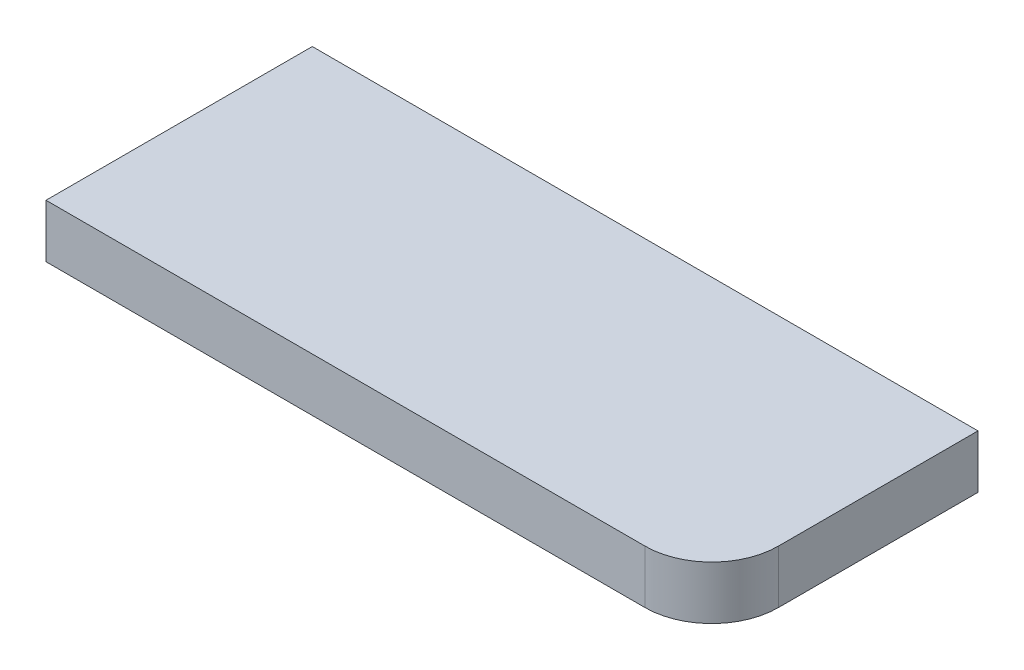
SolidWorks part; units mm, degrees
material "Клен"
ref_plane "Спереди" through (0, 0, 0) normal (0, 0, 1) x (1, 0, 0)
ref_plane "Сверху" through (0, 0, 0) normal (0, 1, 0) x (1, 0, 0)
ref_plane "Справа" through (0, 0, 0) normal (1, 0, 0) x (0, 0, -1)
sketch "Эскиз1" plane through (0, 0, 0) normal (0, 1, 0) x (1, 0, 0)
  line L1 (-50, -20) -> (40, -20)
  line L2 (-50, -20) -> (-50, 20)
  line L3 (-50, 20) -> (50, 20)
  line L4 (50, -10) -> (50, 20)
  line L5 (-50, -20) -> (50, 20) construction
  line L6 (-50, 20) -> (50, -20) construction
  arc A0 (40, -20) -> (50, -10) centre (40, -10) ccw
  point P0 (0, 0)
  dimension "D3" = 10
  dimension "D1" = 100
  dimension "D2" = 40
extrude "Бобышка-Вытянуть1" add sketch "Эскиз1" along normal blind 8
